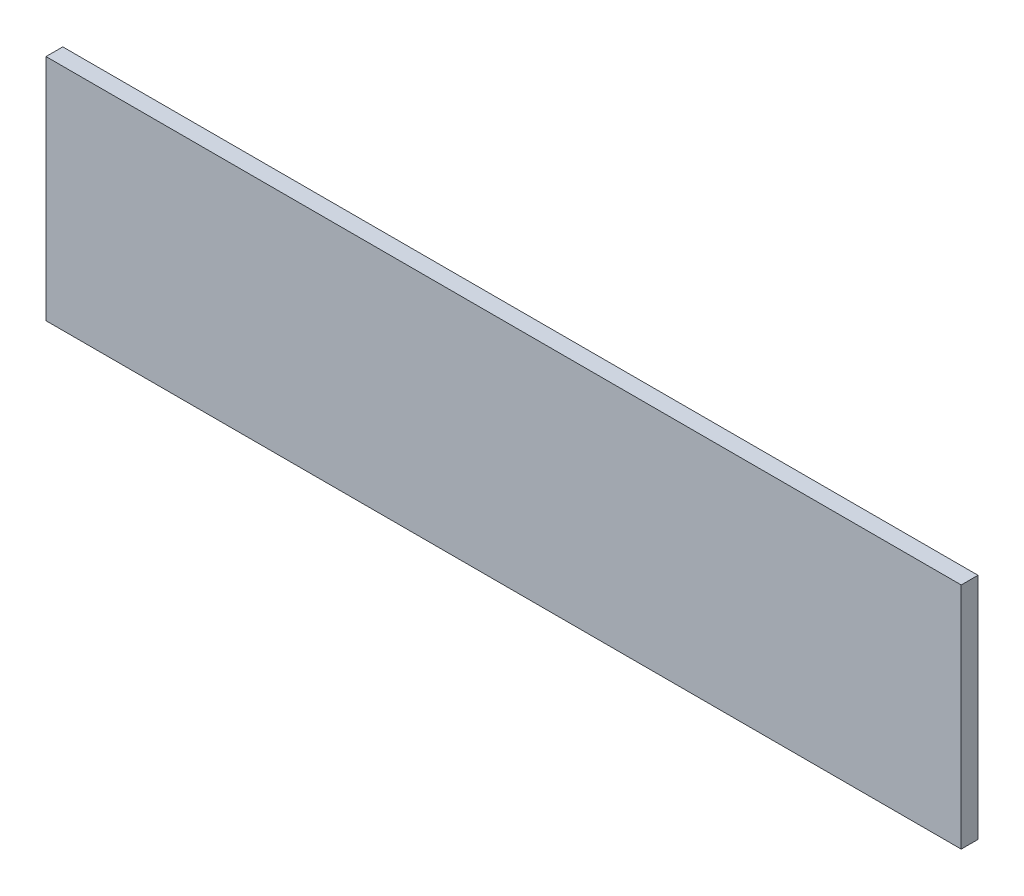
SolidWorks part; units mm, degrees
ref_plane "Front Plane" through (0, 0, 0) normal (0, 0, 1) x (1, 0, 0)
ref_plane "Top Plane" through (0, 0, 0) normal (0, 1, 0) x (1, 0, 0)
ref_plane "Right Plane" through (0, 0, 0) normal (1, 0, 0) x (0, 0, -1)
sketch "Sketch1" plane through (0, 0, 0) normal (0, 0, 1) x (1, 0, 0)
  line L1 (-152.4, -38.1) -> (152.4, -38.1)
  line L2 (-152.4, -38.1) -> (-152.4, 38.1)
  line L3 (-152.4, 38.1) -> (152.4, 38.1)
  line L4 (152.4, -38.1) -> (152.4, 38.1)
  line L5 (-152.4, -38.1) -> (152.4, 38.1) construction
  line L6 (-152.4, 38.1) -> (152.4, -38.1) construction
  point P0 (0, 0)
  dimension "D1" = 304.8
  dimension "D2" = 76.2
extrude "Boss-Extrude1" add sketch "Sketch1" along normal blind 5.588
